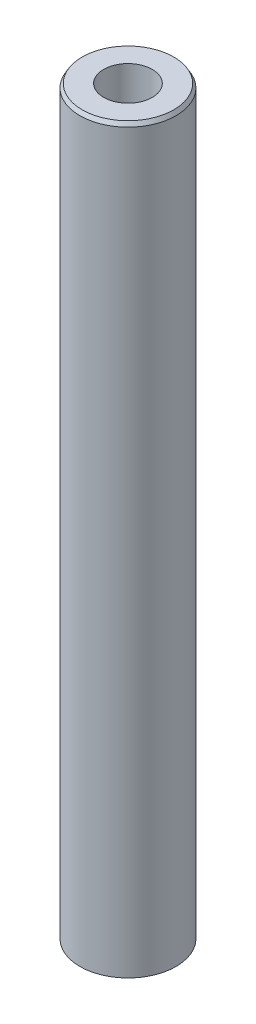
SolidWorks part; units mm, degrees
ref_plane "Front Plane" through (0, 0, 0) normal (0, 0, 1) x (1, 0, 0)
ref_plane "Top Plane" through (0, 0, 0) normal (0, 1, 0) x (1, 0, 0)
ref_plane "Right Plane" through (0, 0, 0) normal (1, 0, 0) x (0, 0, -1)
sketch "Sketch1" plane through (0, 0, 0) normal (0, 1, 0) x (1, 0, 0)
  circle A0 centre (0, 0) radius 32.5
  dimension "SHAFT_OD" = 65
extrude "Boss-Extrude1" add sketch "Sketch1" along normal blind 502.3012
sketch "Sketch2" plane through (0, 0, 0) normal (0, 1, 0) x (1, 0, 0)
  circle A0 centre (0, 0) radius 16.4253
  dimension "BORE_D" = 32.8506
extrude "Cut-Extrude1" cut sketch "Sketch2" along normal through all
chamfer "Chamfer1" distance 2.6803 angle 30 2 edges at (0, 502.3012, 32.5) (0, 0, 32.5) first distance on face at (0, 502.3012, 32.5) first distance on face at (0, 0, 16.4253)
